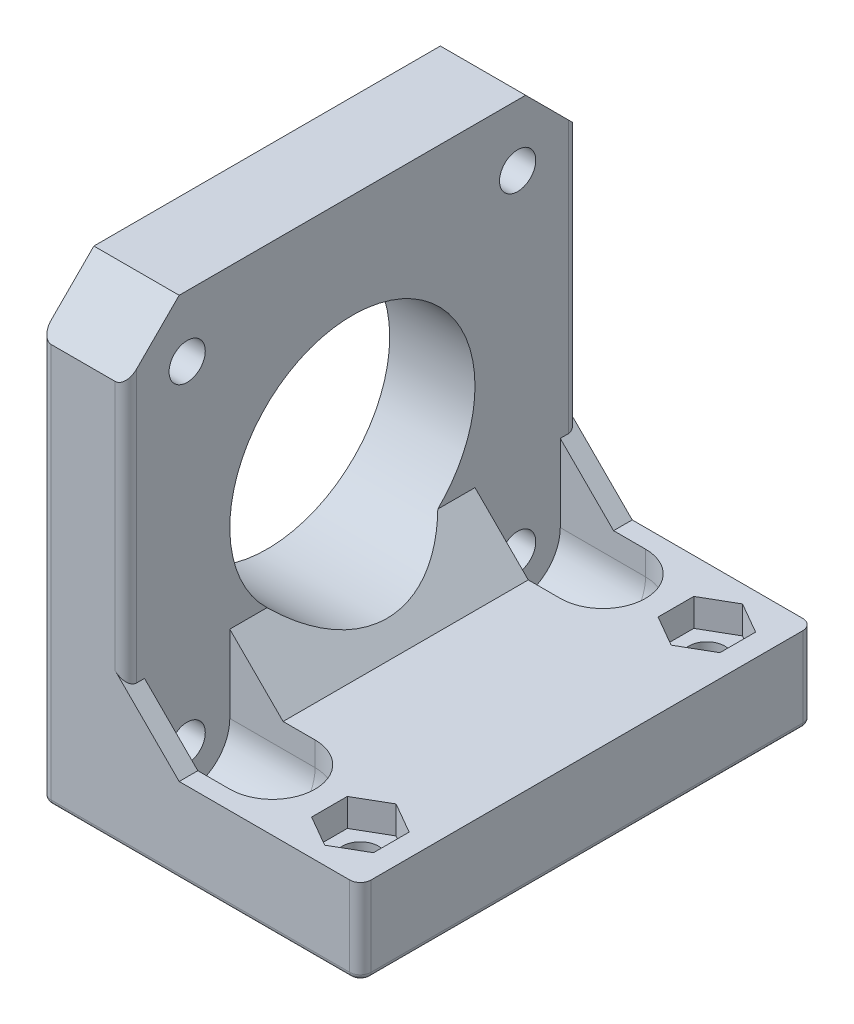
SolidWorks part; units mm, degrees
ref_plane "Front Plane" through (0, 0, 0) normal (0, 0, 1) x (1, 0, 0)
ref_plane "Top Plane" through (0, 0, 0) normal (0, 1, 0) x (1, 0, 0)
ref_plane "Right Plane" through (0, 0, 0) normal (1, 0, 0) x (0, 0, -1)
sketch "Sketch1" plane through (0, 0, 0) normal (1, 0, 0) x (0, 0, -1)
  line L1 (-21.25, 21.25) -> (21.25, 21.25)
  line L2 (-21.25, 21.25) -> (-21.25, -21.25)
  line L3 (-21.25, -21.25) -> (21.25, -21.25)
  line L4 (21.25, 21.25) -> (21.25, -21.25)
  line L5 (-21.25, 21.25) -> (21.25, -21.25) construction
  line L6 (-21.25, -21.25) -> (21.25, 21.25) construction
  point P0 (0, 0)
  dimension "D1" = 42.5
  dimension "D2" = 42.5
extrude "Boss-Extrude1" add sketch "Sketch1" along normal blind 8
sketch "Sketch2" plane through (8, 0, 0) normal (1, 0, 0) x (0, 0, -1)
  line L0 (0, 21.25) -> (0, -21.25) construction
  line L1 (21.25, 21.25) -> (-21.25, 21.25) construction
  line L2 (-21.25, -21.25) -> (21.25, -21.25) construction
  line L3 (-21.25, 0) -> (21.25, 0) construction
  line L4 (-21.25, 21.25) -> (-21.25, -21.25) construction
  line L5 (21.25, -21.25) -> (21.25, 21.25) construction
  line L6 (0, 15.5) -> (15.5, 15.5) construction
  line L7 (0, 15.5) -> (-15.5, 15.5) construction
  line L8 (0, -15.5) -> (15.5, -15.5) construction
  line L9 (0, -15.5) -> (-15.5, -15.5) construction
  circle A0 centre (-15.5, 15.5) radius 1.7
  circle A1 centre (15.5, 15.5) radius 1.7
  circle A2 centre (-15.5, -15.5) radius 1.7
  circle A3 centre (15.5, -15.5) radius 1.7
  circle A4 centre (0, 0) radius 11.5
  dimension "D7" = 3.4
  dimension "D8" = 3.4
  dimension "D9" = 3.4
  dimension "D10" = 3.4
  dimension "D11" = 23
  dimension "D1" = 15.5
  dimension "D2" = 15.5
  dimension "D3" = 15.5
  dimension "D4" = 15.5
  dimension "D5" = 15.5
  dimension "D6" = 15.5
extrude "Cut-Extrude1" cut sketch "Sketch2" against normal blind 35
sketch "Sketch3" plane through (8, 0, 0) normal (1, 0, 0) x (0, 0, -1)
  line L0 (0, -21.25) -> (0, 21.25) construction
  line L1 (-21.25, -21.25) -> (21.25, -21.25) construction
  line L2 (21.25, 21.25) -> (-21.25, 21.25) construction
  line L3 (-21.25, -13.25) -> (-18.8072, -13.25) construction
  line L4 (-21.25, -13.25) -> (21.25, -13.25)
  line L5 (-21.25, -13.25) -> (-21.25, -21.25)
  line L6 (-21.25, -21.25) -> (21.25, -21.25)
  line L7 (21.25, -13.25) -> (21.25, -21.25)
  line L8 (-21.25, -13.25) -> (21.25, -21.25) construction
  line L9 (-21.25, -21.25) -> (21.25, -13.25) construction
  line L10 (-19.5, -15.5) -> (-19.5, -13.25)
  line L11 (-12.132, -13.25) -> (-9.132, -13.25) construction
  line L12 (12.1928, -13.25) -> (9.1928, -13.25) construction
  line L13 (-11.5, -15.5) -> (-11.5, -13.25)
  line L14 (11.5, -15.5) -> (11.5, -13.25)
  line L15 (19.5, -15.5) -> (19.5, -13.25)
  circle A0 centre (-15.5, -15.5) radius 4
  circle A1 centre (15.5, -15.5) radius 4
  point P6 (0, -17.25)
  dimension "D3" = 8
  dimension "D4" = 8
  dimension "D1" = 8
  dimension "D2" = 42.5
  dimension "D5" = 3
  dimension "D6" = 3
extrude "Boss-Extrude2" add sketch "Sketch3" along normal blind 22
sketch "Sketch5" plane through (0, -13.25, 0) normal (0, 1, 0) x (1, 0, 0)
  line L5 (30, -21.25) -> (8, -21.25) construction
  line L6 (30, 21.25) -> (20, 21.25)
  line L7 (30, 21.25) -> (30, -21.25)
  line L8 (30, -21.25) -> (20, -21.25)
  line L9 (20, 21.25) -> (20, -21.25)
  dimension "D1" = 10
extrude "Boss-Extrude3" add sketch "Sketch5" against normal up to surface (8 mm away) up to face at (15, -21.25, 0)
fillet "Fillet1" radius 4 3 edges at (20, -14.375, 11.5) (20, -19.5, 15.5) (20, -14.375, 19.5)
fillet "Fillet2" radius 4 3 edges at (20, -14.375, -11.5) (20, -19.5, -15.5) (20, -14.375, -19.5)
chamfer "Chamfer2" distance 5 angle 45 3 edges at (8, -13.25, -20.375) (8, -13.25, 20.375) (8, -13.25, 0)
sketch "Sketch6" plane through (0, -13.25, 0) normal (0, 1, 0) x (1, 0, 0)
  line L0 (25, 21.25) -> (25, -21.25) construction
  line L1 (30, 21.25) -> (13, 21.25) construction
  line L2 (30, -21.25) -> (13, -21.25) construction
  line L3 (30, -21.25) -> (30, 21.25) construction
  line L4 (25, 12.9014) -> (27.9, 14.5757)
  line L5 (27.9, 14.5757) -> (27.9, 17.9243)
  line L6 (27.9, 17.9243) -> (25, 19.5986)
  line L7 (25, 19.5986) -> (22.1, 17.9243)
  line L8 (22.1, 17.9243) -> (22.1, 14.5757)
  line L9 (22.1, 14.5757) -> (25, 12.9014)
  line L10 (25, -19.5986) -> (27.9, -17.9243)
  line L11 (27.9, -17.9243) -> (27.9, -14.5757)
  line L12 (27.9, -14.5757) -> (25, -12.9014)
  line L13 (25, -12.9014) -> (22.1, -14.5757)
  line L14 (22.1, -14.5757) -> (22.1, -17.9243)
  line L15 (22.1, -17.9243) -> (25, -19.5986)
  circle A0 centre (25, 16.25) radius 2.9 construction
  circle A1 centre (25, -16.25) radius 2.9 construction
  dimension "D1" = 5.8
  dimension "D2" = 5.8
  dimension "D3" = 5
  dimension "D4" = 5
  dimension "D5" = 5
extrude "Cut-Extrude2" cut sketch "Sketch6" against normal blind 2.6
sketch "Sketch7" plane through (0, -15.85, 0) normal (0, 1, 0) x (1, 0, 0)
  line L0 (22.1, 16.25) -> (27.9, 16.25) construction
  line L1 (22.1, 17.9243) -> (22.1, 14.5757) construction
  line L2 (27.9, 14.5757) -> (27.9, 17.9243) construction
  line L3 (22.1, -16.25) -> (27.9, -16.25) construction
  line L4 (22.1, -14.5757) -> (22.1, -17.9243) construction
  line L5 (27.9, -17.9243) -> (27.9, -14.5757) construction
  circle A0 centre (25, 16.25) radius 1.7
  circle A1 centre (25, -16.25) radius 1.7
  dimension "D1" = 3.4
  dimension "D2" = 3.4
extrude "Cut-Extrude3" cut sketch "Sketch7" against normal blind 10.6
chamfer "Chamfer3" distance 5 angle 45 2 edges at (4, 21.25, -21.25) (4, 21.25, 21.25)
fillet "Fillet3" radius 1 4 edges at (30, -17.25, -21.25) (0, -2.5, -21.25) (0, -2.5, 21.25) (30, -17.25, 21.25)
fillet "Fillet4" radius 1 2 edges at (8, 4, -21.25) (8, 4, 21.25)
fillet "Fillet5" radius 0.5 8 edges at (0.2929, -21.25, -20.9571) (15, -21.25, -21.25) (29.7071, -21.25, -20.9571) (30, -21.25, 0) (29.7071, -21.25, 20.9571) (0.2929, -21.25, 20.9571) (15, -21.25, 21.25) (0, -21.25, 0)
